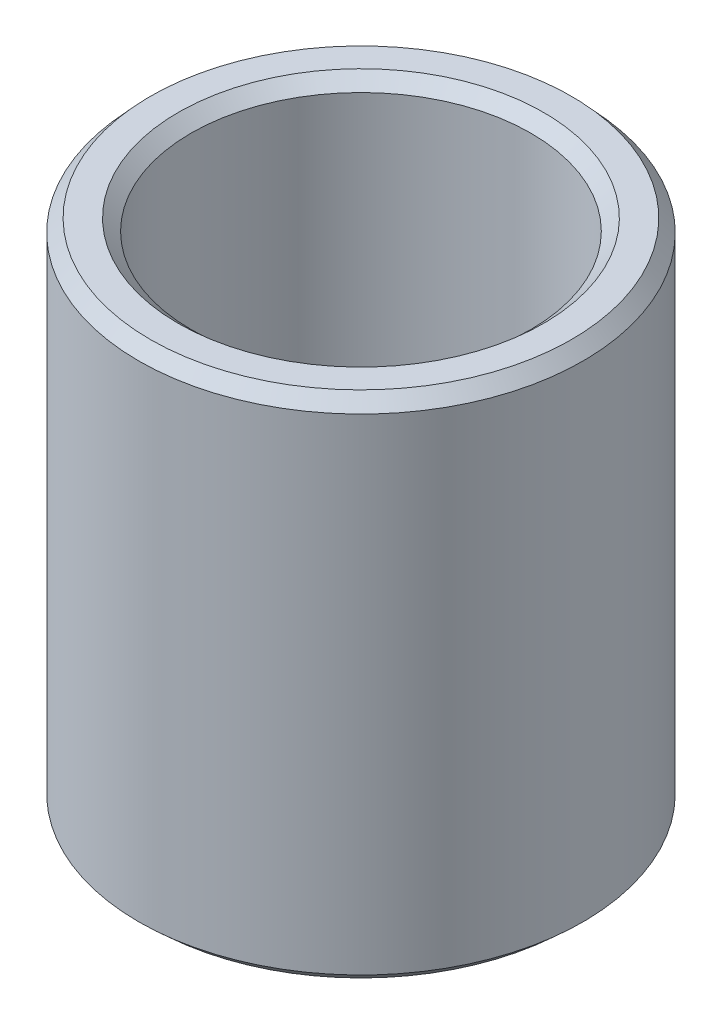
SolidWorks part; units mm, degrees
ref_plane "Front Plane" through (0, 0, 0) normal (0, 0, 1) x (1, 0, 0)
ref_plane "Top Plane" through (0, 0, 0) normal (0, 1, 0) x (1, 0, 0)
ref_plane "Right Plane" through (0, 0, 0) normal (1, 0, 0) x (0, 0, -1)
sketch "Sketch1" plane through (0, 0, 0) normal (0, 1, 0) x (1, 0, 0)
  circle A0 centre (0, 0) radius 60
  dimension "SLEEVE_OD" = 120
extrude "Boss-Extrude1" add sketch "Sketch1" along normal blind 137.7234
sketch "Sketch2" plane through (0, 0, 0) normal (0, 1, 0) x (1, 0, 0)
  circle A0 centre (0, 0) radius 45.8937
  dimension "BORE_D" = 91.7875
extrude "Cut-Extrude1" cut sketch "Sketch2" along normal through all
chamfer "Chamfer1" distance 3.443 angle 42.292 4 edges at (0, 137.7234, 45.8937) (0, 0, 45.8937) (0, 0, 60) (0, 137.7234, 60) first distance on face at (0, 137.7234, 45.8937) first distance on face at (0, 0, 45.8937) first distance on face at (0, 137.7234, 60)
